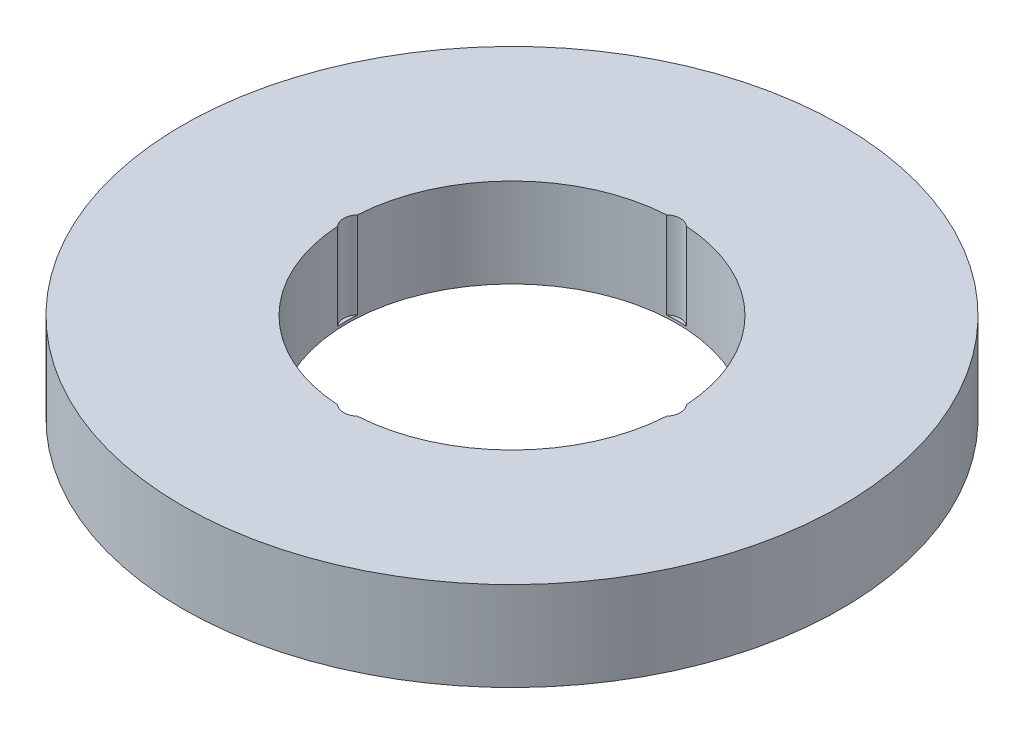
SolidWorks part; units mm, degrees
ref_plane "Front Plane" through (0, 0, 0) normal (0, 0, 1) x (1, 0, 0)
ref_plane "Top Plane" through (0, 0, 0) normal (0, 1, 0) x (1, 0, 0)
ref_plane "Right Plane" through (0, 0, 0) normal (1, 0, 0) x (0, 0, -1)
sketch "Sketch1" plane through (0, 0, 0) normal (0, 1, 0) x (1, 0, 0)
  circle A0 centre (0, 0) radius 85
  dimension "FLANGE_OD" = 170
extrude "Boss-Extrude1" add sketch "Sketch1" along normal blind 23
sketch "Sketch2" plane through (0, 0, 0) normal (0, 1, 0) x (1, 0, 0)
  circle A0 centre (0, 0) radius 42.5
  dimension "BORE_D" = 85
extrude "Cut-Extrude1" cut sketch "Sketch2" along normal through all
sketch "Sketch3" plane through (0, 23, 0) normal (0, 1, 0) x (1, 0, 0)
  circle A0 centre (0, 0) radius 39.606 construction
  circle A1 centre (-39.606, 0) radius 3.799
  dimension "BOLT_D" = 7.5979
  dimension "BOLT_PCD" = 79.2119
extrude "Cut-Extrude2" cut sketch "Sketch3" against normal blind 22.3423
pattern_circular "CirPattern1" count 4 over 360 about axis through (0, 0, 0) along (0, 1, 0) of "Cut-Extrude2"
